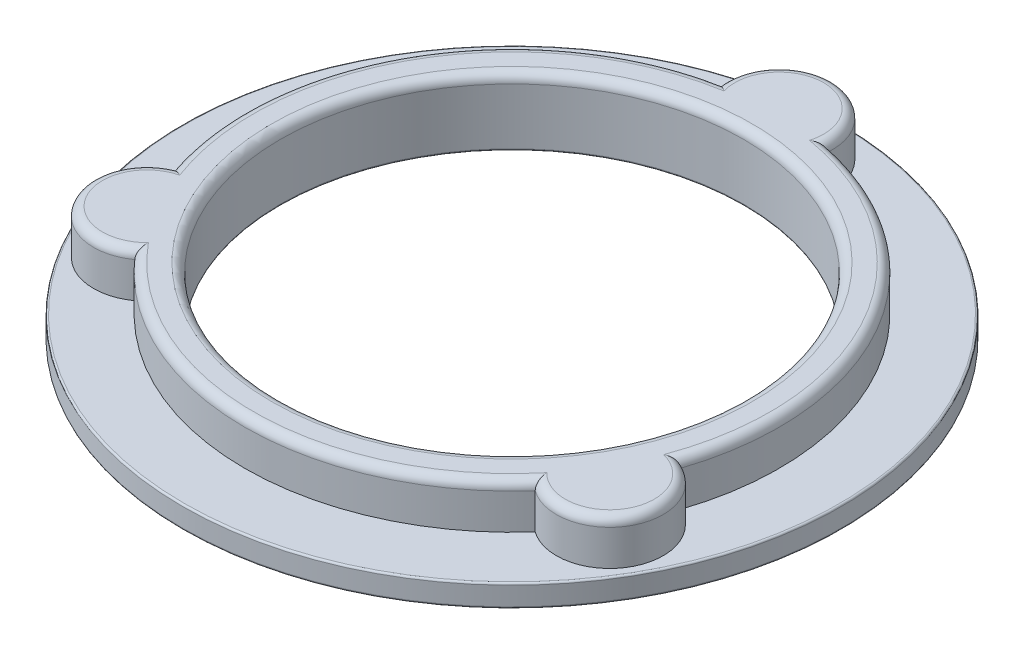
SolidWorks part; units mm, degrees
ref_plane "Front" through (0, 0, 0) normal (0, 0, 1) x (1, 0, 0)
ref_plane "Top" through (0, 0, 0) normal (0, 1, 0) x (1, 0, 0)
ref_plane "Right" through (0, 0, 0) normal (1, 0, 0) x (0, 0, -1)
sketch "Sketch1" plane through (0, 0, 0) normal (0, 1, 0) x (1, 0, 0)
  circle A0 centre (0, 0) radius 13
  circle A1 centre (0, 0) radius 18.5
  dimension "D1" = 26
  dimension "D2" = 5.5
extrude "Boss-Extrude1" add sketch "Sketch1" along normal blind 1.25
sketch "Sketch2" plane through (0, 1.25, 0) normal (0, 1, 0) x (1, 0, 0)
  circle A0 centre (0, 0) radius 13 construction
  circle A1 centre (0, 0) radius 13
  circle A2 centre (0, 0) radius 15
  arc A3 (2.985, 14.7) -> (-2.985, 14.7) centre (0, 15) ccw
  arc A4 (11.2381, -9.9351) -> (14.2231, -4.7649) centre (12.9904, -7.5) ccw
  arc A5 (-14.2231, -4.7649) -> (-11.2381, -9.9351) centre (-12.9904, -7.5) ccw
  point P17 (0, 0)
  circle M2 centre (0, 0) radius 13
  dimension "D2" = 6
  dimension "D4" = 3
  dimension "D1" = 2
  dimension "D3" = 3
extrude "Boss-Extrude2" add sketch "Sketch2" along normal blind 2.5 contours A2 A3 | A2 M2 | A2 A5 | A2 A4 region at (14.3858, 1.25, 2.3457) region at (0, 1.25, -16.2177) region at (14.0449, 1.25, 8.1088) region at (-14.0449, 1.25, 8.1088)
fillet "Fillet1" radius 0.5 7 edges at (0, 3.75, 13) (12.9904, 3.75, -7.5) (15.5885, 3.75, 9) (0, 3.75, 15) (-15.5885, 3.75, 9) (-12.9904, 3.75, -7.5) (0, 3.75, -18)
fillet "Fillet2" radius 0.1 3 edges at (0, 0, 18.5) (0, 1.25, 18.5) (0, 0, 13)
